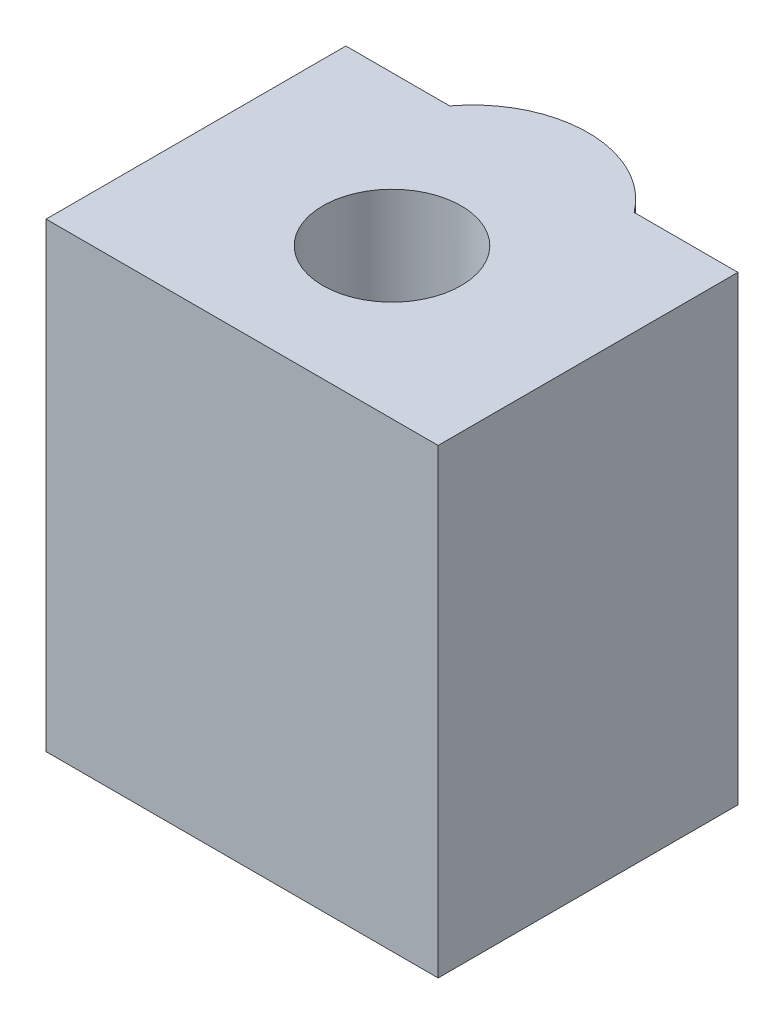
SolidWorks part; units mm, degrees
ref_plane "Front Plane" through (0, 0, 0) normal (0, 0, 1) x (1, 0, 0)
ref_plane "Top Plane" through (0, 0, 0) normal (0, 1, 0) x (1, 0, 0)
ref_plane "Right Plane" through (0, 0, 0) normal (1, 0, 0) x (0, 0, -1)
sketch "Sketch1" plane through (0, 0, 0) normal (0, 1, 0) x (1, 0, 0)
  line L0 (8.5, 0) -> (8.5, 10) construction
  line L1 (0, 0) -> (17, 0)
  line L2 (0, 0) -> (0, 13)
  line L3 (0, 13) -> (4.5, 13)
  line L4 (17, 0) -> (17, 13)
  line L5 (12.5, 13) -> (17, 13)
  arc A0 (4.5, 13) -> (12.5, 13) centre (8.5, 10) cw
  point P8 (8.5, 15)
  point P11 (8.4203, 10)
  dimension "D1" = 17
  dimension "D2" = 13
  dimension "D3" = 15
  dimension "D4" = 8
extrude "Boss-Extrude1" add sketch "Sketch1" along normal blind 20
sketch "Sketch2" plane through (0, 20, 0) normal (0, 1, 0) x (1, 0, 0)
  line L0 (0, 6.5) -> (8.5, 6.5) construction
  line L1 (0, 13) -> (0, 0) construction
  line L2 (8.5, 0) -> (8.5, 6.5) construction
  line L3 (0, 0) -> (17, 0) construction
  circle A0 centre (8.5, 6.5) radius 3
  point P3 (8.5, 6.5413)
  point P10 (8.4643, 6.5)
  point P11 (8.5439, 6.5)
  dimension "D1" = 6
extrude "Cut-Extrude1" cut sketch "Sketch2" against normal offset from surface (12 mm away) 12 up to face at (8.5, 20, -9)
sketch "Sketch3" plane through (0, 8, 0) normal (0, 1, 0) x (1, 0, 0)
  circle A0 centre (8.5, 6.5) radius 1.75
  circle A1 centre (8.5, 6.5) radius 3 construction
  dimension "D1" = 3.5
extrude "Cut-Extrude2" cut sketch "Sketch3" against normal through all
